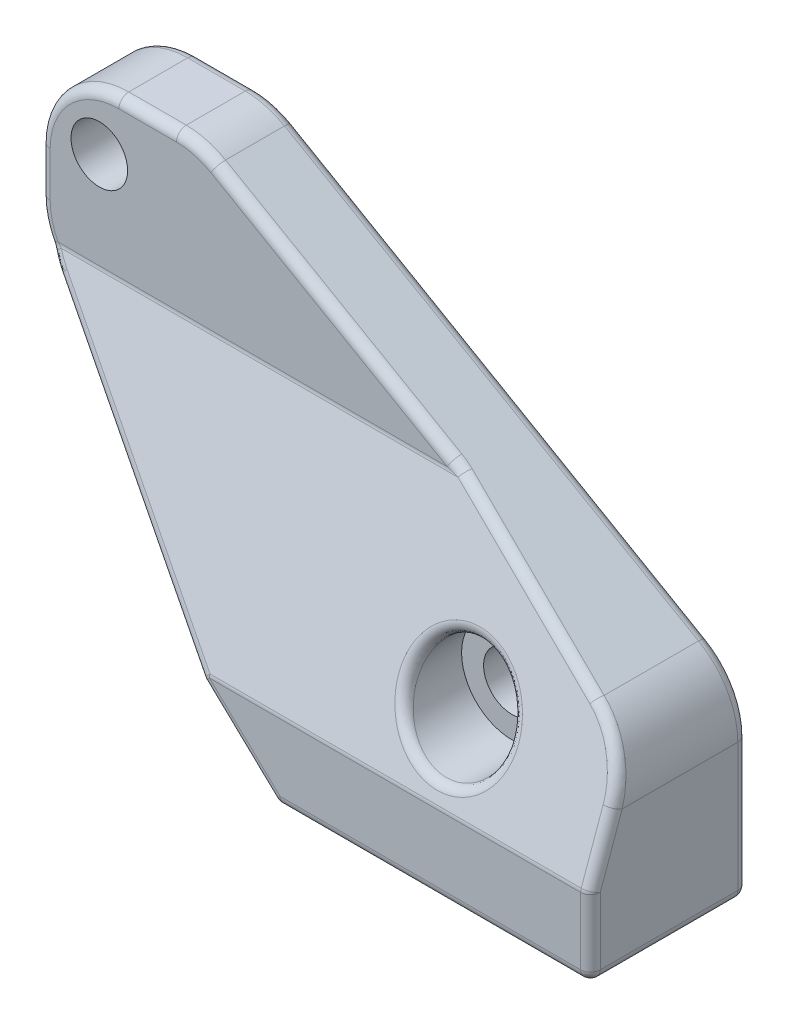
SolidWorks part; units mm, degrees
ref_plane "Front Plane" through (0, 0, 0) normal (0, 0, 1) x (1, 0, 0)
ref_plane "Top Plane" through (0, 0, 0) normal (0, 1, 0) x (1, 0, 0)
ref_plane "Right Plane" through (0, 0, 0) normal (1, 0, 0) x (0, 0, -1)
sketch "Sketch8" plane through (0, 0, 0) normal (0, 0, 1) x (1, 0, 0)
  line L0 (0, 0) -> (-25.4, 0)
  line L3 (-50.8, 36.83) -> (-38.1, 36.83)
  line L4 (-38.1, 36.83) -> (0, 14.833)
  line L5 (0, 14.833) -> (0, 0)
  line L6 (-50.8, 36.83) -> (-50.8, 24.13)
  line L7 (-50.8, 36.83) -> (-50.8, -7.62) construction
  line L8 (-50.8, 24.13) -> (-25.4, 0)
  circle A0 centre (-12.7, 11.8269) radius 2.286 construction
  circle A1 centre (-46.0375, 32.0675) radius 2.286 construction
  circle A2 centre (-12.7, 11.8269) radius 2.286
  circle A3 centre (-46.0375, 32.0675) radius 2.286
  dimension "D1" = 12.7
  dimension "D2" = 12.7
  dimension "D3" = 150
  dimension "D4" = 25.4
extrude "Boss-Extrude1" add sketch "Sketch8" along normal blind 12.7
sketch "Sketch9" plane through (0, 0, 0) normal (0, -1, 0) x (1, 0, 0)
  line L0 (0, 12.7) -> (0, 0) construction
  line L4 (-25.4, 12.7) -> (0, 12.7) construction
  circle A0 centre (-6.35, 6.35) radius 1.905
  circle A1 centre (-19.05, 6.35) radius 1.905
  point P6 (-19.05, 6.35)
  dimension "D2" = 6.35
  dimension "D4" = 3.81
  dimension "D1" = 6.35
  dimension "D5" = 12.7
  dimension "D3" = 2
extrude "Cut-Extrude4" cut sketch "Sketch9" against normal blind 12.7
sketch "Sketch10" plane through (-50.8, 0, 0) normal (-1, 0, 0) x (0, 0, 1)
  line L0 (6.35, 36.83) -> (6.35, 24.13)
  line L1 (12.7, 36.83) -> (0, 36.83) construction
  line L2 (6.35, 24.13) -> (12.7, 6.35)
  line L3 (12.7, 24.13) -> (12.7, 0) construction
  line L4 (12.7, 6.35) -> (12.7, 36.83)
  line L5 (12.7, 36.83) -> (12.7, 24.13) construction
  line L6 (12.7, 36.83) -> (6.35, 36.83)
  line L7 (12.7, 0) -> (0, 0) construction
  dimension "D1" = 12.7
  dimension "D2" = 6.35
extrude "Cut-Extrude5" cut sketch "Sketch10" against normal through all
sketch "Sketch11" plane through (0, 0, 12.7) normal (0, 0, 1) x (1, 0, 0)
  circle A0 centre (-12.7, 11.8269) radius 4.064
  dimension "D1" = 8.128
extrude "Cut-Extrude6" cut sketch "Sketch11" against normal offset from surface (6.35 mm away) 6.35 up to face at (-10.414, 11.8269, 0)
fillet "Fillet1" radius 6.35 4 edges at (-50.8, 24.13, 3.175) (-50.8, 36.83, 3.175) (-38.1, 36.83, 3.175) (0, 14.833, 4.8352)
fillet "Fillet2" radius 0.7937 29 edges at (-9.639, 20.398, 7.6828) (-0.8507, 14.3418, 9.8458) (-0.8507, 14.3418, 0) (-19.9007, 26.3227, 0) (-38.158, 36.6136, 0) (-42.1257, 36.83, 0) (-48.9401, 34.9701, 0) (-50.8, 28.6681, 0) (-50.285, 24.3511, 0) (-49.5908, 23.1285, 6.7077) (-26.3647, 30.0546, 6.35) (-38.158, 36.6136, 6.35) (-42.1257, 36.83, 6.35) (-48.9401, 34.9701, 6.35) (-50.6444, 25.4588, 6.35) (0, 0, 6.35) (0, 3.175, 12.7) (0, 8.7584, 11.8399) (0, 5.5834, 0) (-28.7421, 3.175, 12.7) (-25.4, 0, 6.35) (-37.1118, 11.1262, 0) (-40.4539, 14.3012, 9.8603) (-12.7, 0, 12.7) (-12.7, 0, 0) (-16.0421, 6.35, 12.7) (-33.144, 24.13, 6.35) (-50.8, 28.6681, 6.35) (-12.7, 7.7629, 12.1954)
